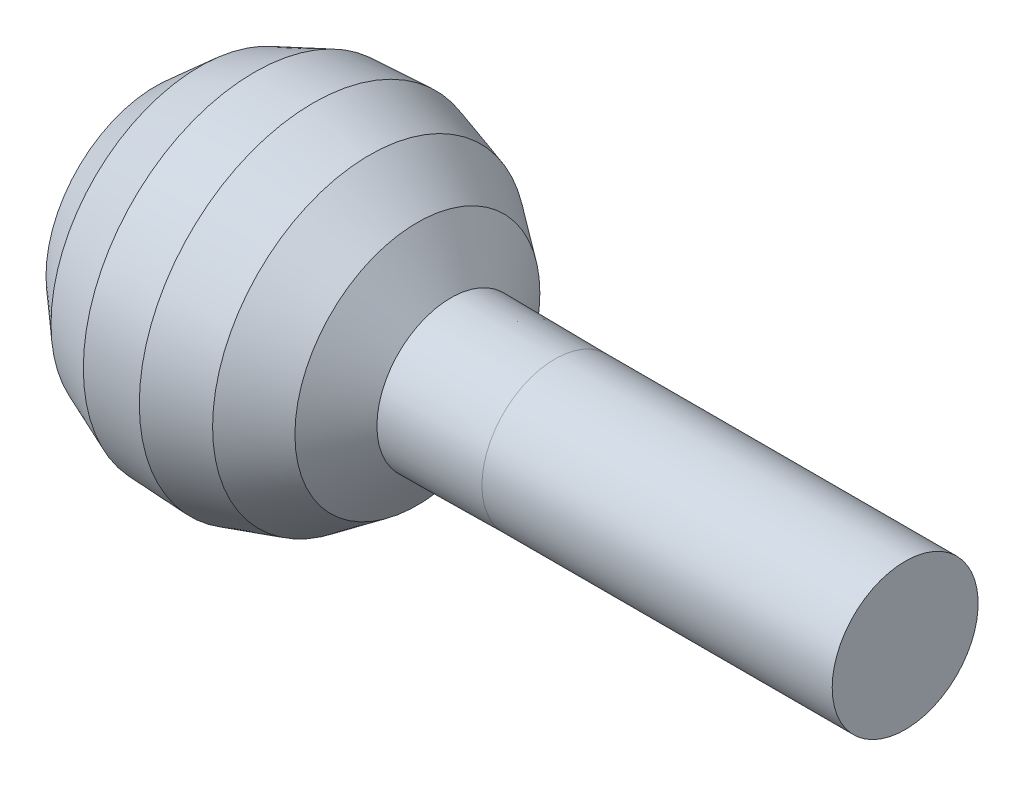
SolidWorks part; units mm, degrees
ref_plane "Front Plane" through (0, 0, 0) normal (0, 0, 1) x (1, 0, 0)
ref_plane "Top Plane" through (0, 0, 0) normal (0, 1, 0) x (1, 0, 0)
ref_plane "Right Plane" through (0, 0, 0) normal (1, 0, 0) x (0, 0, -1)
sketch "Ball_Stud Sketch" plane through (0, 0, 0) normal (0, 0, 1) x (1, 0, 0)
  line L0 (-1000, 0) -> (1000, 0) construction
  line L1 (-7.5, 0) -> (-7.3301, 0.9952)
  line L2 (-7.3301, 0.9952) -> (-6.8397, 1.8778)
  line L3 (-6.8397, 1.8778) -> (-6.0842, 2.5476)
  line L4 (-6.0842, 2.5476) -> (-5.1493, 2.9289)
  line L5 (-5.1493, 2.9289) -> (-4.1409, 2.9784)
  line L6 (-4.1409, 2.9784) -> (-3.1731, 2.6906)
  line L7 (-3.1731, 2.6906) -> (-2.3557, 2.0981)
  line L8 (-2.3557, 2.0981) -> (-1.7811, 1.2679)
  line L9 (-1.7811, 1.2679) -> (0, 1.25)
  line L10 (0, 1.25) -> (6, 1.25)
  line L11 (6, 1.25) -> (6, 0)
  line L12 (6, 0) -> (-7.5, 0)
revolve "Ball_Stud" add sketch "Ball_Stud Sketch" angle 360 about L0
ref_axis "Engine Axis" through (6.675, 0, 0) along (-1, 0, 0)
sketch "Ball Points" plane through (0, 0, 0) normal (0, 0, 1) x (1, 0, 0)
  point P0 (-4.5, 0)
  point P1 (-4.5, 5)
